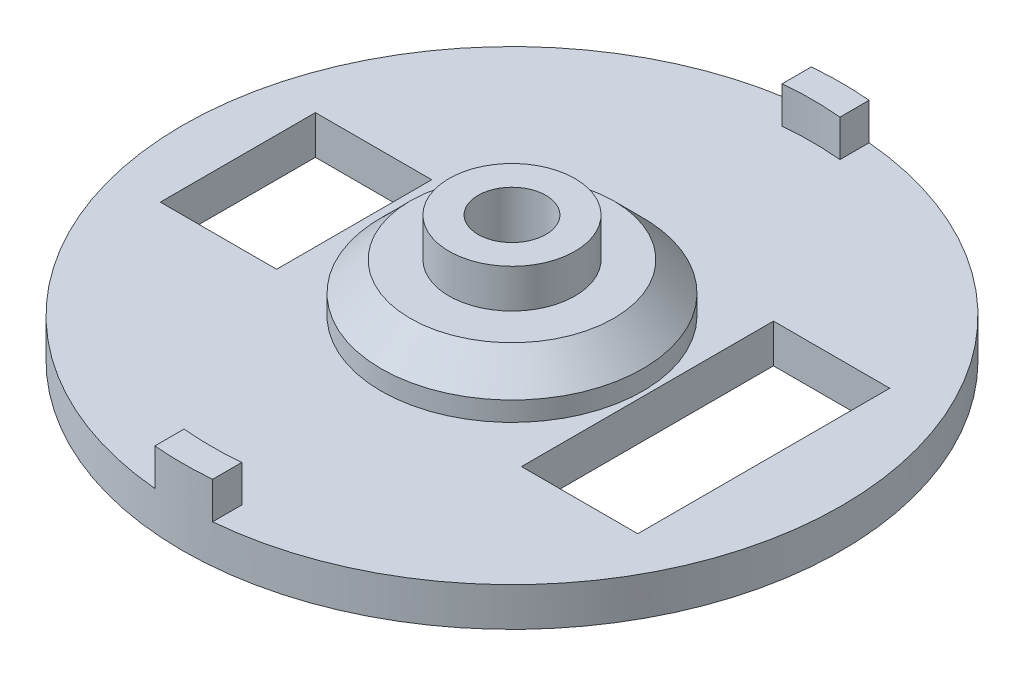
SolidWorks part; units mm, degrees
ref_plane "Front Plane" through (0, 0, 0) normal (0, 0, 1) x (1, 0, 0)
ref_plane "Top Plane" through (0, 0, 0) normal (0, 1, 0) x (1, 0, 0)
ref_plane "Right Plane" through (0, 0, 0) normal (1, 0, 0) x (0, 0, -1)
sketch "Sketch1" plane through (0, 0, 0) normal (0, 1, 0) x (1, 0, 0)
  line L1 (6.99, -6.5) -> (12.99, -6.5)
  line L2 (6.99, -6.5) -> (6.99, 6.5)
  line L3 (6.99, 6.5) -> (12.99, 6.5)
  line L4 (12.99, -6.5) -> (12.99, 6.5)
  line L5 (6.99, -6.5) -> (12.99, 6.5) construction
  line L6 (6.99, 6.5) -> (12.99, -6.5) construction
  line L7 (-14.142, -4) -> (-8.142, -4)
  line L8 (-14.142, -4) -> (-14.142, 4)
  line L9 (-14.142, 4) -> (-8.142, 4)
  line L10 (-8.142, -4) -> (-8.142, 4)
  line L11 (-14.142, -4) -> (-8.142, 4) construction
  line L12 (-14.142, 4) -> (-8.142, -4) construction
  line L13 (4.6477, 0) -> (2.3238, 4.025)
  line L14 (2.3238, 4.025) -> (-2.3238, 4.025)
  line L15 (-2.3238, 4.025) -> (-4.6477, 0)
  line L16 (-4.6477, 0) -> (-2.3238, -4.025)
  line L17 (-2.3238, -4.025) -> (2.3238, -4.025)
  line L18 (2.3238, -4.025) -> (4.6477, 0)
  circle A0 centre (0, 0) radius 17
  circle A1 centre (0, 0) radius 15.5
  circle A2 centre (0, 0) radius 1.75
  circle A3 centre (0, 0) radius 4.025 construction
  circle A4 centre (0, 0) radius 3.25
  circle A5 centre (0, 0) radius 6.75
  point P3 (9.99, 0)
  point P8 (-11.142, 0)
  dimension "D1" = 34
  dimension "D8" = 3.5
  dimension "D9" = 8.05
  dimension "D2" = 13
  dimension "D3" = 6
  dimension "D4" = 8
  dimension "D6" = 6.99
  dimension "D7" = 8.142
  dimension "D5" = 1.5
  dimension "D10" = 1.5
  dimension "D11" = 3.5
extrude "Boss-Extrude1" add sketch "Sketch1" along normal blind 2 contours A0 A1 | A1 A5 L10 L7 L8 L9 L4 L1 L2 L3 | A5 L18 L17 L16 L15 L14 L13 | L17 L18 L13 L14 L15 L16 A4 | A4 A2 region at (3.3793, 0, 1.951) region at (-16.5192, 0, 0) region at (-15.0616, 0, 0) region at (-3.1581, 0, 0) region at (-6.5591, 0, 0)
extrude "Boss-Extrude2" add sketch "Sketch1<3>" along normal blind 4.5 contours A5 L18 L17 L16 L15 L14 L13 | A2 | L18 L13 L14 L15 L16 L17 region at (0, 0, 0) region at (-6.5591, 0, 0)
sketch "Sketch1<3>" plane through (0, 0, 0) normal (0, 1, 0) x (1, 0, 0) same geometry as "Sketch1"
extrude "Boss-Extrude3" add sketch "Sketch1<4>" along normal blind 6.5 contours A4 A2 region at (-3.1581, 0, 0)
sketch "Sketch1<4>" plane through (0, 0, 0) normal (0, 1, 0) x (1, 0, 0) same geometry as "Sketch1"
extrude "Cut-Extrude1" cut sketch "Sketch1<5>" along normal blind 2.5 contours L17 L18 L13 L14 L15 L16 A4 | A4 A2 region at (3.3793, 0, 1.951) region at (-3.1581, 0, 0)
sketch "Sketch1<5>" plane through (0, 0, 0) normal (0, 1, 0) x (1, 0, 0) same geometry as "Sketch1"
sketch "Sketch2" plane through (0, 2, 0) normal (0, 1, 0) x (1, 0, 0)
  line L0 (0, 17) -> (0, -17) construction
  line L1 (-1.49, 17) -> (-1.49, 15.4282)
  line L2 (1.49, 17) -> (1.49, 15.4282)
  line L3 (-1.49, 17) -> (1.49, 17)
  line L4 (-1.49, -17) -> (1.49, -17)
  line L5 (1.49, -15.4282) -> (1.49, -17)
  line L6 (1.49, 17) -> (1.49, -17) construction
  line L7 (-1.49, -15.4282) -> (-1.49, -17)
  line L8 (-1.49, 17) -> (-1.49, -17) construction
  arc A0 (1.49, 15.4282) -> (-1.49, 15.4282) centre (0, 0) ccw
  circle A1 centre (0, 0) radius 17 construction
  circle A2 centre (0, 0) radius 17
  arc A3 (1.49, 16.9346) -> (-1.49, 16.9346) centre (0, 0) ccw
  circle A4 centre (0, 0) radius 15.5 construction
  arc A5 (-1.49, -16.9346) -> (1.49, -16.9346) centre (0, 0) ccw
  arc A6 (-1.49, -15.4282) -> (1.49, -15.4282) centre (0, 0) ccw
  point P8 (0, 0)
  circle M15 centre (0, 0) radius 17
  dimension "D1" = 0
  dimension "D2" = 1.5
  dimension "D3" = 1.49
  dimension "D4" = 1.49
extrude "Boss-Extrude4" add sketch "Sketch2" along normal blind 1.9 contours A0 L2 L1 M15 | A6 L7 L5 M15 region at (0, 2, -16.2271) region at (0, 2, 16.2271)
sketch "Sketch4" plane through (0, 0, 0) normal (0, -1, 0) x (1, 0, 0)
  line L0 (3.575, 0) -> (-3.575, 0) construction
  line L1 (-2.3238, 4.025) -> (2.3237, 4.025)
  line L2 (-2.3238, 4.025) -> (-2.3238, 4.985)
  line L4 (2.3237, 4.025) -> (2.3237, 4.985)
  line L6 (2.3237, -4.025) -> (2.3237, -4.985)
  line L7 (-2.3238, -4.025) -> (2.3237, -4.025)
  line L8 (-2.3238, -4.025) -> (-2.3237, -4.985)
  arc A0 (2.3237, 4.985) -> (-2.3238, 4.985) centre (0, 0) ccw
  arc A1 (-2.3237, -4.985) -> (2.3237, -4.985) centre (0, 0) ccw
  dimension "D1" = 5.5
extrude "Cut-Extrude2" cut sketch "Sketch4" against normal blind 3
chamfer "Chamfer1" distance 1.5 angle 45 1 edges at (0, 4.5, 6.75)
